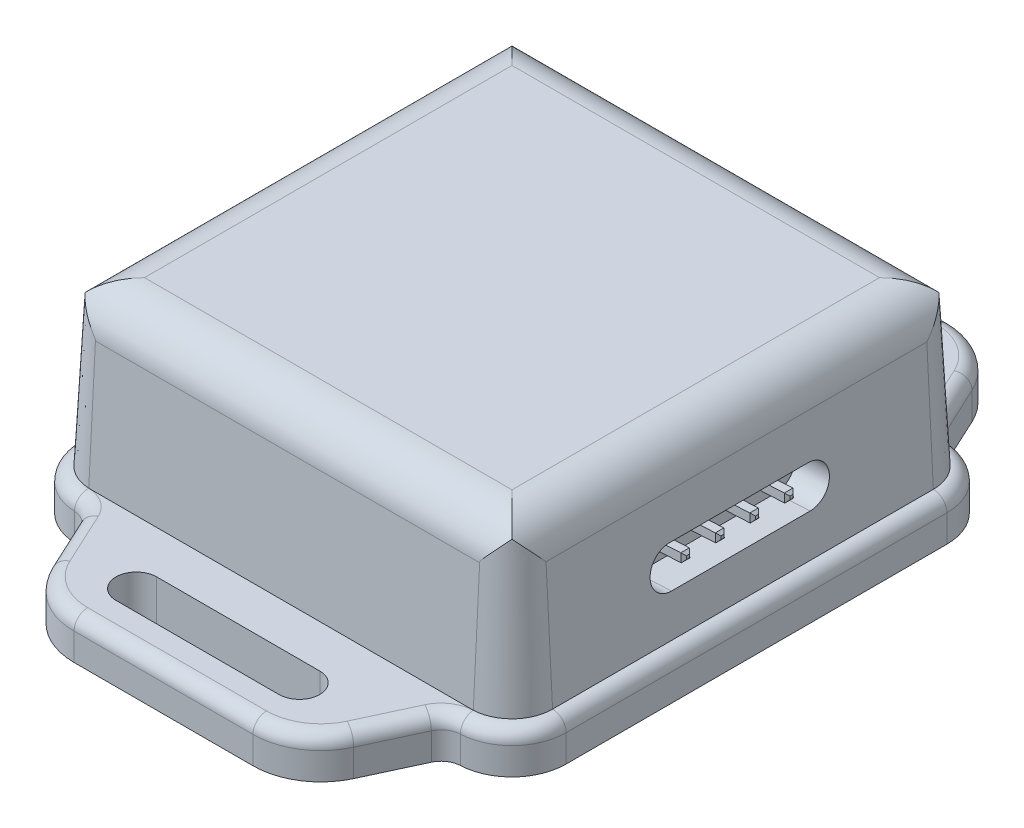
SolidWorks part; units mm, degrees
ref_plane "前视基准面" through (0, 0, 0) normal (0, 0, 1) x (1, 0, 0)
ref_plane "上视基准面" through (0, 0, 0) normal (0, 1, 0) x (1, 0, 0)
ref_plane "右视基准面" through (0, 0, 0) normal (1, 0, 0) x (0, 0, -1)
other "Configuration Table"
sketch "草图1" plane through (0, 0, 0) normal (0, 1, 0) x (1, 0, 0)
  line L0 (0, 28.1752) -> (0, -31.8471) construction
  line L1 (30.4329, 0) -> (-28.5677, 0) construction
  line L2 (6.5835, 25.65) -> (-6.5835, 25.65)
  line L3 (-11.1096, 22.7611) -> (-12.9202, 18.8609)
  line L4 (-18, 14.0146) -> (-18, -13.9854)
  line L5 (11.1096, 22.7611) -> (12.9202, 18.8609)
  line L6 (-18, -14.0146) -> (-18, 13.9854)
  line L7 (-11.1096, -22.7611) -> (-12.9202, -18.8609)
  line L8 (6.5835, -25.65) -> (-6.5835, -25.65)
  line L9 (11.1096, -22.7611) -> (12.9202, -18.8609)
  line L10 (18, 14.0146) -> (18, -14.0146)
  line L11 (-6, 21.65) -> (6, 21.65) construction
  line L12 (-6, 23.15) -> (6, 23.15)
  line L13 (-6, 20.15) -> (6, 20.15)
  line L14 (-6, -21.65) -> (6, -21.65) construction
  line L15 (-6, -23.15) -> (6, -23.15)
  line L16 (-6, -20.15) -> (6, -20.15)
  arc A0 (-6.5835, 25.65) -> (-11.1096, 22.7611) centre (-6.5835, 20.66) ccw
  arc A1 (-12.9202, 18.8609) -> (-14.2005, 18) centre (-14.2716, 19.4883) cw
  arc A2 (-14.2005, 18) -> (-18, 14.0146) centre (-14.01, 14.0146) ccw
  arc A3 (14.2005, 18) -> (18, 14.0146) centre (14.01, 14.0146) cw
  arc A4 (12.9202, 18.8609) -> (14.2005, 18) centre (14.2716, 19.4883) ccw
  arc A5 (6.5835, 25.65) -> (11.1096, 22.7611) centre (6.5835, 20.66) cw
  arc A6 (-14.2005, -18) -> (-18, -14.0146) centre (-14.01, -14.0146) cw
  arc A7 (-12.9202, -18.8609) -> (-14.2005, -18) centre (-14.2716, -19.4883) ccw
  arc A8 (-6.5835, -25.65) -> (-11.1096, -22.7611) centre (-6.5835, -20.66) cw
  arc A9 (6.5835, -25.65) -> (11.1096, -22.7611) centre (6.5835, -20.66) ccw
  arc A10 (12.9202, -18.8609) -> (14.2005, -18) centre (14.2716, -19.4883) cw
  arc A11 (14.2005, -18) -> (18, -14.0146) centre (14.01, -14.0146) ccw
  arc A12 (-6, 23.15) -> (-6, 20.15) centre (-6, 21.65) ccw
  arc A13 (6, 20.15) -> (6, 23.15) centre (6, 21.65) ccw
  arc A14 (-6, -23.15) -> (-6, -20.15) centre (-6, -21.65) cw
  arc A15 (6, -20.15) -> (6, -23.15) centre (6, -21.65) cw
  point P17 (0, 21.65)
  point P30 (0, 25.65)
  point P49 (0, -21.65)
  dimension "D1" = 4.99
  dimension "D3" = 1.49
  dimension "D4" = 3.99
  dimension "D9" = 114.902
  dimension "D2" = 4.3
  dimension "D5" = 28
  dimension "D6" = 36
  dimension "D7" = 36
  dimension "D8" = 51.3
  dimension "D10" = 12
  dimension "D11" = 3
  dimension "D12" = 2.5
extrude "凸台-拉伸1" add sketch "草图1" along normal blind 3 contours A10 A11 L10 A3 A4 L5 A5 L2 A0 L3 A1 A2 L4 L6 A6 A7 L7 A8 L8 A9 L9
fillet "圆角1" radius 1 20 edges at (0, 3, -25.65) (9.2682, 3, -24.8662) (12.0149, 3, -20.811) (13.4402, 3, -18.2518) (16.8979, 3, -16.7677) (18, 3, 0) (16.8979, 3, 16.7677) (13.4402, 3, 18.2518) (12.0149, 3, 20.811) (9.2682, 3, 24.8662) (0, 3, 25.65) (-9.2682, 3, 24.8662) (-12.0149, 3, 20.811) (-13.4402, 3, 18.2518) (-16.8979, 3, 16.7677) (-18, 3, 0) (-16.8979, 3, -16.7677) (-13.4402, 3, -18.2518) (-12.0149, 3, -20.811) (-9.2682, 3, -24.8662)
sketch "草图2" plane through (0, 3, 0) normal (0, 1, 0) x (1, 0, 0)
  line L0 (-14.1528, 17.0011) -> (14.1528, 17.0011)
  line L3 (-17, 14.0146) -> (-17, -14.0146) construction
  line L4 (-17, 14.0146) -> (-17, -14.0146)
  line L5 (-33.4774, 0) -> (30.5779, 0) construction
  line L6 (0, 37.56) -> (0, -38.0798) construction
  line L7 (-14.1528, -17.0011) -> (14.1528, -17.0011)
  line L8 (17, 14.0146) -> (17, -14.0146)
  arc A1 (17, 14.0146) -> (14.1528, 17.0011) centre (14.01, 14.0146) ccw construction
  arc A2 (17, 14.0146) -> (14.1528, 17.0011) centre (14.01, 14.0146) ccw
  arc A3 (-14.1528, 17.0011) -> (-17, 14.0146) centre (-14.01, 14.0146) ccw construction
  arc A4 (-14.1528, 17.0011) -> (-17, 14.0146) centre (-14.01, 14.0146) ccw
  arc A5 (14.1528, -17.0011) -> (17, -14.0146) centre (14.01, -14.0146) ccw construction
  arc A6 (14.1528, -17.0011) -> (17, -14.0146) centre (14.01, -14.0146) ccw
  arc A7 (-17, -14.0146) -> (-14.1528, -17.0011) centre (-14.01, -14.0146) ccw construction
  arc A8 (-17, -14.0146) -> (-14.1528, -17.0011) centre (-14.01, -14.0146) ccw
extrude "凸台-拉伸2" add sketch "草图2" along normal blind 12 draft 3
fillet "圆角3" radius 3 2 edges at (0, 15, 16.3722) (0, 15, -16.3722)
fillet "圆角4" radius 3 2 edges at (-16.3711, 15, 0) (16.3711, 15, 0)
sketch "草图4" plane through (17.1102, 0.8967, 0) normal (0.9986, 0.0523, 0) x (0, 0, -1)
  line L0 (-5.1, 6.6062) -> (5.1, 6.6062) construction
  line L1 (-5.1, 8.1062) -> (5.1, 8.1062)
  line L2 (-5.1, 5.1062) -> (5.1, 5.1062)
  line L3 (0, -5.4344) -> (0, 18.9612) construction
  line L12 (-14.0146, 2.1062) -> (14.0146, 2.1062) construction
  arc A0 (-5.1, 8.1062) -> (-5.1, 5.1062) centre (-5.1, 6.6062) ccw
  arc A1 (5.1, 5.1062) -> (5.1, 8.1062) centre (5.1, 6.6062) ccw
  point P6 (0, 6.6062)
  dimension "D4" = 13.2
  dimension "D3" = 3
  dimension "D1" = 3
extrude "切除-拉伸1" cut sketch "草图4" against normal blind 2.54
sketch "草图5" plane through (14.5737, 0.7638, 0) normal (0.9986, 0.0523, 0) x (0, 0, -1)
  line L0 (-22.0926, 6.6062) -> (23.5876, 6.6062) construction
  line L1 (5.1, 8.1062) -> (-5.1, 8.1062) construction
  line L2 (-5.1, 5.1062) -> (5.1, 5.1062) construction
  line L3 (0, -4.5915) -> (0, 16.7538) construction
  line L4 (-1.585, 6.9212) -> (-1.585, 6.2912)
  line L5 (-4.125, 6.9212) -> (-3.495, 6.9212)
  line L6 (-4.125, 6.9212) -> (-4.125, 6.2912)
  line L7 (-4.125, 6.2912) -> (-3.495, 6.2912)
  line L8 (-3.495, 6.9212) -> (-3.495, 6.2912)
  line L9 (-4.125, 6.9212) -> (-3.495, 6.2912) construction
  line L10 (-4.125, 6.2912) -> (-3.495, 6.9212) construction
  line L11 (-1.585, 6.9212) -> (-0.955, 6.9212)
  line L12 (-0.955, 6.9212) -> (-0.955, 6.2912)
  line L13 (-1.585, 6.2912) -> (-0.955, 6.2912)
  line L14 (0.955, 6.9212) -> (0.955, 6.2912)
  line L15 (0.955, 6.9212) -> (1.585, 6.9212)
  line L16 (1.585, 6.9212) -> (1.585, 6.2912)
  line L17 (0.955, 6.2912) -> (1.585, 6.2912)
  line L18 (3.495, 6.9212) -> (3.495, 6.2912)
  line L19 (3.495, 6.9212) -> (4.125, 6.9212)
  line L20 (4.125, 6.9212) -> (4.125, 6.2912)
  line L21 (3.495, 6.2912) -> (4.125, 6.2912)
  point P6 (-3.81, 6.6062)
  dimension "D2" = 3.81
  dimension "D3" = 4
  dimension "D1" = 0.63
extrude "凸台-拉伸3" add sketch "草图5" along normal up to surface (2.54 mm away) up to face at (16.7645, 7.4938, 0)
chamfer "倒角2" distance 0.2 angle 45 4 edges at (16.7645, 7.4938, 3.495) (16.781, 7.1793, 3.81) (16.7645, 7.4938, 4.125) (16.748, 7.8084, 3.81)
chamfer "倒角3" distance 0.2 angle 45 12 edges at (16.781, 7.1793, -3.81) (16.7645, 7.4938, -3.495) (16.748, 7.8084, -3.81) (16.7645, 7.4938, -4.125) (16.781, 7.1793, 1.27) (16.7645, 7.4938, 1.585) (16.748, 7.8084, 1.27) (16.7645, 7.4938, 0.955) (16.781, 7.1793, -1.27) (16.7645, 7.4938, -0.955) (16.748, 7.8084, -1.27) (16.7645, 7.4938, -1.585)
sketch "草图6" plane through (-17.1102, 0.8967, 0) normal (-0.9986, 0.0523, 0) x (0, 0, 1)
  line L0 (0, -5.5512) -> (0, 21.1352) construction
  line L1 (-2.9, 6.3562) -> (2.9, 6.3562) construction
  line L2 (-2.9, 7.6062) -> (2.9, 7.6062)
  line L3 (-2.9, 5.1062) -> (2.9, 5.1062)
  line L4 (-14.0146, 2.1062) -> (14.0146, 2.1062) construction
  arc A0 (-2.9, 7.6062) -> (-2.9, 5.1062) centre (-2.9, 6.3562) ccw
  arc A1 (2.9, 5.1062) -> (2.9, 7.6062) centre (2.9, 6.3562) ccw
  point P5 (0, 6.3562)
  dimension "D1" = 8.3
  dimension "D2" = 2.5
  dimension "D3" = 3
extrude "切除-拉伸2" cut sketch "草图6" against normal blind 5.08
sketch "草图7" plane through (-12.0372, 0.6308, 0) normal (-0.9986, 0.0523, 0) x (0, 0, 1)
  line L0 (-18.2903, 6.3562) -> (21.1328, 6.3562) construction
  line L1 (-2.5, 6.3562) -> (2.5, 6.3562) construction
  line L2 (-2.9, 5.1062) -> (2.9, 5.1062)
  line L3 (2.9, 7.6062) -> (-2.9, 7.6062)
  line L4 (-2.9, 5.1062) -> (2.9, 5.1062)
  line L5 (2.9, 7.6062) -> (-2.9, 7.6062)
  line L6 (-2.5, 6.4312) -> (2.5, 6.4312)
  line L7 (-2.5, 6.2812) -> (2.5, 6.2812)
  line L8 (0, -3.0213) -> (0, 10.281) construction
  arc A0 (-2.5, 6.4312) -> (-2.5, 6.2812) centre (-2.5, 6.3562) ccw
  arc A1 (2.5, 6.2812) -> (2.5, 6.4312) centre (2.5, 6.3562) ccw
  arc A2 (-2.9, 7.6062) -> (-2.9, 5.1062) centre (-2.9, 6.3562) ccw
  arc A3 (2.9, 5.1062) -> (2.9, 7.6062) centre (2.9, 6.3562) ccw
  arc A4 (-2.9, 7.6062) -> (-2.9, 5.1062) centre (-2.9, 6.3562) ccw
  arc A5 (2.9, 5.1062) -> (2.9, 7.6062) centre (2.9, 6.3562) ccw
  point P10 (0, 6.3562)
  dimension "D2" = 0.15
  dimension "D3" = 5
  dimension "D1" = 0
extrude "凸台-拉伸4" add sketch "草图7" along normal blind 2.54 contours L6 A1 L7 A0
sketch "草图8" plane through (0, 0, 0) normal (0, -1, 0) x (1, 0, 0)
  circle A0 centre (14.01, 14.0146) radius 1.5
  circle A1 centre (-14.01, -14.0146) radius 1.5
  dimension "D1" = 3
  dimension "D2" = 3
extrude "切除-拉伸3" cut sketch "草图8" against normal blind 0.1
